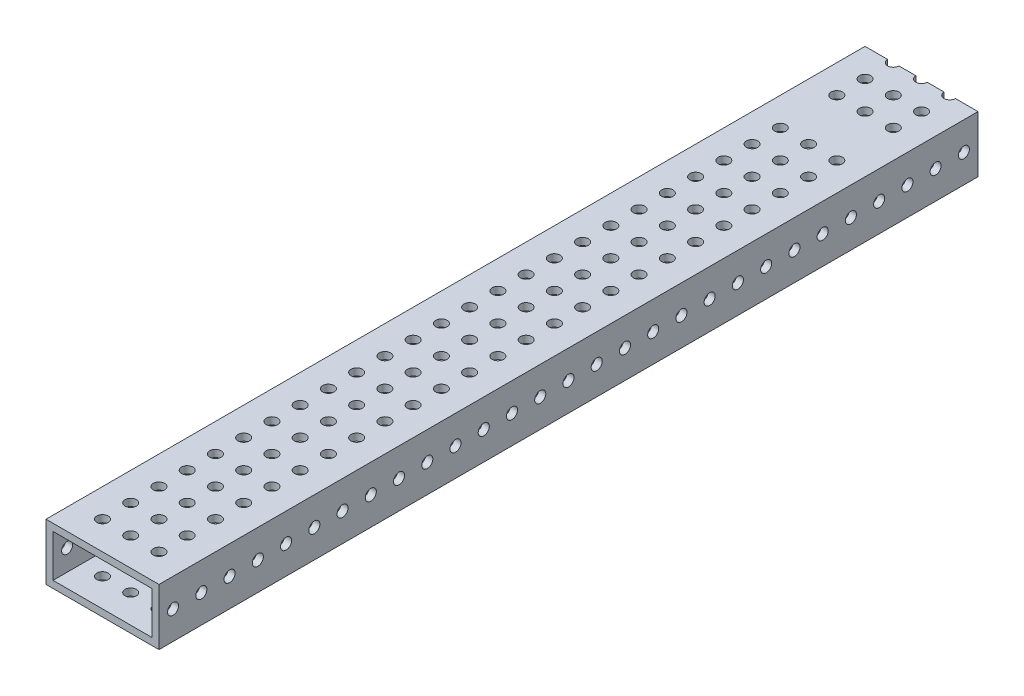
SolidWorks part; units mm, degrees
material "6061-T6 (SS)"
ref_plane "Front Plane" through (0, 0, 0) normal (0, 0, 1) x (1, 0, 0)
ref_plane "Top Plane" through (0, 0, 0) normal (0, 1, 0) x (1, 0, 0)
ref_plane "Right Plane" through (0, 0, 0) normal (1, 0, 0) x (0, 0, -1)
sketch "Sketch1" plane through (0, 0, 0) normal (0, 0, 1) x (1, 0, 0)
  line L0 (-22.225, 9.525) -> (22.225, 9.525)
  line L1 (-25.4, 12.7) -> (25.4, 12.7)
  line L2 (-25.4, 12.7) -> (-25.4, -12.7)
  line L3 (-25.4, -12.7) -> (25.4, -12.7)
  line L4 (25.4, 12.7) -> (25.4, -12.7)
  line L5 (22.225, 9.525) -> (22.225, -9.525)
  line L6 (-22.225, -9.525) -> (22.225, -9.525)
  line L7 (-22.225, 9.525) -> (-22.225, -9.525)
  line L8 (-25.4, 12.7) -> (25.4, -12.7) construction
  line L9 (25.4, 12.7) -> (-25.4, -12.7) construction
  point P5 (0, 0)
  dimension "D1" = 50.8
  dimension "D2" = 25.4
  dimension "D3" = 3.175
extrude "Boss-Extrude1" add sketch "Sketch1" along normal mid plane 368.3
sketch "Sketch2" plane through (0, 12.7, 0) normal (0, 1, 0) x (1, 0, 0)
  line L0 (25.4, -184.15) -> (-25.4, -184.15) construction
  line L1 (-25.4, -184.15) -> (-25.4, 184.15) construction
  line L2 (-12.7, -171.45) -> (0, -171.45) construction
  line L3 (0, -171.45) -> (12.7, -171.45) construction
  line L4 (25.4, 184.15) -> (-25.4, 184.15) construction
  circle A0 centre (0, -171.45) radius 2.5527
  circle A1 centre (12.7, -171.45) radius 2.5527
  circle A2 centre (-12.7, -171.45) radius 2.5527
  circle A3 centre (-12.7, -158.75) radius 2.5527
  circle A4 centre (0, -158.75) radius 2.5527
  circle A5 centre (12.7, -158.75) radius 2.5527
  circle A6 centre (-12.7, -146.05) radius 2.5527
  circle A7 centre (0, -146.05) radius 2.5527
  circle A8 centre (12.7, -146.05) radius 2.5527
  circle A9 centre (-12.7, -133.35) radius 2.5527
  circle A10 centre (0, -133.35) radius 2.5527
  circle A11 centre (12.7, -133.35) radius 2.5527
  circle A12 centre (-12.7, -120.65) radius 2.5527
  circle A13 centre (0, -120.65) radius 2.5527
  circle A14 centre (12.7, -120.65) radius 2.5527
  circle A15 centre (-12.7, -107.95) radius 2.5527
  circle A16 centre (0, -107.95) radius 2.5527
  circle A17 centre (12.7, -107.95) radius 2.5527
  circle A18 centre (-12.7, -95.25) radius 2.5527
  circle A19 centre (0, -95.25) radius 2.5527
  circle A20 centre (12.7, -95.25) radius 2.5527
  circle A21 centre (-12.7, -82.55) radius 2.5527
  circle A22 centre (0, -82.55) radius 2.5527
  circle A23 centre (12.7, -82.55) radius 2.5527
  circle A24 centre (-12.7, -69.85) radius 2.5527
  circle A25 centre (0, -69.85) radius 2.5527
  circle A26 centre (12.7, -69.85) radius 2.5527
  circle A27 centre (-12.7, -57.15) radius 2.5527
  circle A28 centre (0, -57.15) radius 2.5527
  circle A29 centre (12.7, -57.15) radius 2.5527
  circle A30 centre (-12.7, -44.45) radius 2.5527
  circle A31 centre (0, -44.45) radius 2.5527
  circle A32 centre (12.7, -44.45) radius 2.5527
  circle A33 centre (-12.7, -31.75) radius 2.5527
  circle A34 centre (0, -31.75) radius 2.5527
  circle A35 centre (12.7, -31.75) radius 2.5527
  circle A36 centre (-12.7, -19.05) radius 2.5527
  circle A37 centre (0, -19.05) radius 2.5527
  circle A38 centre (12.7, -19.05) radius 2.5527
  circle A39 centre (-12.7, -6.35) radius 2.5527
  circle A40 centre (0, -6.35) radius 2.5527
  circle A41 centre (12.7, -6.35) radius 2.5527
  circle A42 centre (-12.7, 6.35) radius 2.5527
  circle A43 centre (0, 6.35) radius 2.5527
  circle A44 centre (12.7, 6.35) radius 2.5527
  circle A45 centre (-12.7, 19.05) radius 2.5527
  circle A46 centre (0, 19.05) radius 2.5527
  circle A47 centre (12.7, 19.05) radius 2.5527
  circle A48 centre (-12.7, 31.75) radius 2.5527
  circle A49 centre (0, 31.75) radius 2.5527
  circle A50 centre (12.7, 31.75) radius 2.5527
  circle A51 centre (-12.7, 44.45) radius 2.5527
  circle A52 centre (0, 44.45) radius 2.5527
  circle A53 centre (12.7, 44.45) radius 2.5527
  circle A54 centre (-12.7, 57.15) radius 2.5527
  circle A55 centre (0, 57.15) radius 2.5527
  circle A56 centre (12.7, 57.15) radius 2.5527
  circle A57 centre (-12.7, 69.85) radius 2.5527
  circle A58 centre (0, 69.85) radius 2.5527
  circle A59 centre (12.7, 69.85) radius 2.5527
  circle A60 centre (-12.7, 82.55) radius 2.5527
  circle A61 centre (0, 82.55) radius 2.5527
  circle A62 centre (12.7, 82.55) radius 2.5527
  circle A63 centre (-12.7, 95.25) radius 2.5527
  circle A64 centre (0, 95.25) radius 2.5527
  circle A65 centre (12.7, 95.25) radius 2.5527
  circle A66 centre (-12.7, 107.95) radius 2.5527
  circle A67 centre (0, 107.95) radius 2.5527
  circle A68 centre (12.7, 107.95) radius 2.5527
  circle A69 centre (-12.7, 120.65) radius 2.5527
  circle A70 centre (0, 120.65) radius 2.5527
  circle A71 centre (12.7, 120.65) radius 2.5527
  circle A72 centre (-12.7, 133.35) radius 2.5527
  circle A73 centre (0, 133.35) radius 2.5527
  circle A74 centre (12.7, 133.35) radius 2.5527
  circle A75 centre (-12.7, 146.05) radius 2.5527 construction
  circle A76 centre (0, 146.05) radius 2.5527 construction
  circle A77 centre (12.7, 146.05) radius 2.5527 construction
  circle A78 centre (-12.7, 158.75) radius 2.5527
  circle A79 centre (0, 158.75) radius 2.5527
  circle A80 centre (12.7, 158.75) radius 2.5527
  circle A81 centre (-12.7, 171.45) radius 2.5527
  circle A82 centre (0, 171.45) radius 2.5527
  circle A83 centre (12.7, 171.45) radius 2.5527
  circle A84 centre (-12.7, 184.15) radius 2.5527
  circle A85 centre (0, 184.15) radius 2.5527
  circle A86 centre (12.7, 184.15) radius 2.5527
  circle A87 centre (-12.7, 196.85) radius 2.5527
  circle A88 centre (0, 196.85) radius 2.5527
  circle A89 centre (12.7, 196.85) radius 2.5527
  circle A90 centre (-12.7, 209.55) radius 2.5527
  circle A91 centre (0, 209.55) radius 2.5527
  circle A92 centre (12.7, 209.55) radius 2.5527
  circle A93 centre (-12.7, 222.25) radius 2.5527
  circle A94 centre (0, 222.25) radius 2.5527
  circle A95 centre (12.7, 222.25) radius 2.5527
  circle A96 centre (-12.7, 234.95) radius 2.5527
  circle A97 centre (0, 234.95) radius 2.5527
  circle A98 centre (12.7, 234.95) radius 2.5527
  circle A99 centre (-12.7, 247.65) radius 2.5527
  circle A100 centre (0, 247.65) radius 2.5527
  circle A101 centre (12.7, 247.65) radius 2.5527
  circle A108 centre (-12.7, 273.05) radius 2.5527 [skipped]
  circle A109 centre (0, 273.05) radius 2.5527 [skipped]
  circle A110 centre (12.7, 273.05) radius 2.5527 [skipped]
  circle A111 centre (-12.7, 260.35) radius 2.5527 [skipped]
  circle A112 centre (0, 260.35) radius 2.5527 [skipped]
  circle A113 centre (12.7, 260.35) radius 2.5527 [skipped]
  circle A114 centre (12.7, 260.35) radius 2.5527
  circle A115 centre (0, 260.35) radius 2.5527
  circle A116 centre (-12.7, 260.35) radius 2.5527
  circle A117 centre (12.7, 273.05) radius 2.5527
  circle A118 centre (0, 273.05) radius 2.5527
  circle A119 centre (-12.7, 273.05) radius 2.5527
  circle A120 centre (12.7, 285.75) radius 2.5527
  circle A121 centre (0, 285.75) radius 2.5527
  circle A122 centre (-12.7, 285.75) radius 2.5527
  circle A123 centre (12.7, 298.45) radius 2.5527
  circle A124 centre (0, 298.45) radius 2.5527
  circle A125 centre (-12.7, 298.45) radius 2.5527
  circle A126 centre (12.7, 311.15) radius 2.5527
  circle A127 centre (0, 311.15) radius 2.5527
  circle A128 centre (-12.7, 311.15) radius 2.5527
  circle A129 centre (12.7, 323.85) radius 2.5527
  circle A130 centre (0, 323.85) radius 2.5527
  circle A131 centre (-12.7, 323.85) radius 2.5527
  circle A132 centre (12.7, 336.55) radius 2.5527
  circle A133 centre (0, 336.55) radius 2.5527
  circle A134 centre (-12.7, 336.55) radius 2.5527
  circle A135 centre (12.7, 349.25) radius 2.5527
  circle A136 centre (0, 349.25) radius 2.5527
  circle A137 centre (-12.7, 349.25) radius 2.5527
  circle A138 centre (12.7, 361.95) radius 2.5527
  circle A139 centre (0, 361.95) radius 2.5527
  circle A140 centre (-12.7, 361.95) radius 2.5527
  circle A141 centre (12.7, 374.65) radius 2.5527
  circle A142 centre (0, 374.65) radius 2.5527
  circle A143 centre (-12.7, 374.65) radius 2.5527
  circle A144 centre (12.7, 387.35) radius 2.5527
  circle A145 centre (0, 387.35) radius 2.5527
  circle A146 centre (-12.7, 387.35) radius 2.5527
  circle A147 centre (12.7, 400.05) radius 2.5527
  circle A148 centre (0, 400.05) radius 2.5527
  circle A149 centre (-12.7, 400.05) radius 2.5527
  circle A150 centre (12.7, 412.75) radius 2.5527
  circle A151 centre (0, 412.75) radius 2.5527
  circle A152 centre (-12.7, 412.75) radius 2.5527
  dimension "D2" = 5.1054
  dimension "D4" = 12.7
  dimension "D1" = 12.7
  dimension "D3" = 25.4
  dimension "D6" = 12.7
  dimension "D7" = 63.5
  dimension "D5" = 36
  dimension "D8" = 14
extrude "Cut-Extrude1" cut sketch "Sketch2" against normal through all
sketch "Sketch4" plane through (25.4, 0, 0) normal (1, 0, 0) x (0, 0, -1)
  line L1 (-184.15, -12.7) -> (-184.15, 12.7) construction
  line L2 (-184.15, -12.7) -> (184.15, -12.7) construction
  circle A2 centre (-177.8, 0) radius 2.4892
  circle A3 centre (-165.1, 0) radius 2.4892
  circle A16 centre (-152.4, 0) radius 2.4892
  circle A17 centre (-139.7, 0) radius 2.4892
  circle A18 centre (-127, 0) radius 2.4892
  circle A19 centre (254, 0) radius 2.4892
  circle A20 centre (266.7, 0) radius 2.4892
  circle A21 centre (279.4, 0) radius 2.4892
  circle A22 centre (292.1, 0) radius 2.4892
  circle A23 centre (304.8, 0) radius 2.4892
  circle A24 centre (317.5, 0) radius 2.4892
  circle A25 centre (330.2, 0) radius 2.4892
  circle A26 centre (342.9, 0) radius 2.4892
  circle A27 centre (355.6, 0) radius 2.4892
  circle A28 centre (368.3, 0) radius 2.4892
  circle A29 centre (381, 0) radius 2.4892
  circle A30 centre (393.7, 0) radius 2.4892
  circle A31 centre (406.4, 0) radius 2.4892
  circle A32 centre (419.1, 0) radius 2.4892
  circle A35 centre (-114.3, 0) radius 2.4892
  circle A36 centre (-101.6, 0) radius 2.4892
  circle A37 centre (-88.9, 0) radius 2.4892
  circle A38 centre (-76.2, 0) radius 2.4892
  circle A39 centre (-63.5, 0) radius 2.4892
  circle A40 centre (-50.8, 0) radius 2.4892
  circle A41 centre (-38.1, 0) radius 2.4892
  circle A42 centre (-25.4, 0) radius 2.4892
  circle A43 centre (-12.7, 0) radius 2.4892
  circle A44 centre (0, 0) radius 2.4892
  circle A45 centre (12.7, 0) radius 2.4892
  circle A46 centre (25.4, 0) radius 2.4892
  circle A47 centre (38.1, 0) radius 2.4892
  circle A48 centre (50.8, 0) radius 2.4892
  circle A49 centre (63.5, 0) radius 2.4892
  circle A50 centre (76.2, 0) radius 2.4892
  circle A51 centre (88.9, 0) radius 2.4892
  circle A52 centre (101.6, 0) radius 2.4892
  circle A53 centre (114.3, 0) radius 2.4892
  circle A54 centre (127, 0) radius 2.4892
  circle A55 centre (139.7, 0) radius 2.4892
  circle A56 centre (152.4, 0) radius 2.4892
  circle A57 centre (165.1, 0) radius 2.4892
  circle A58 centre (177.8, 0) radius 2.4892
  circle A59 centre (190.5, 0) radius 2.4892
  circle A60 centre (203.2, 0) radius 2.4892
  circle A61 centre (215.9, 0) radius 2.4892
  circle A62 centre (228.6, 0) radius 2.4892
  circle A63 centre (241.3, 0) radius 2.4892
  dimension "D2" = 4.9784
  dimension "D1" = 6.35
  dimension "D3" = 12.7
  dimension "D4" = 12.7
  dimension "D5" = 34
  dimension "D6" = 10
  dimension "D7" = 6
extrude "Cut-Extrude3" cut sketch "Sketch4" against normal through all
